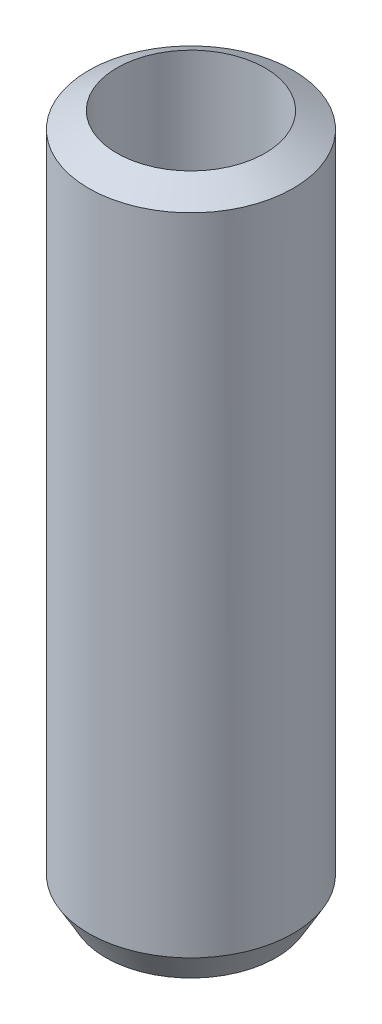
SolidWorks part; units mm, degrees
ref_plane "Front Plane" through (0, 0, 0) normal (0, 0, 1) x (1, 0, 0)
ref_plane "Top Plane" through (0, 0, 0) normal (0, 1, 0) x (1, 0, 0)
ref_plane "Right Plane" through (0, 0, 0) normal (1, 0, 0) x (0, 0, -1)
sketch "Sketch1" plane through (0, 0, 0) normal (0, 1, 0) x (1, 0, 0)
  circle A0 centre (0, 0) radius 30
  dimension "SHAFT_OD" = 60
extrude "Boss-Extrude1" add sketch "Sketch1" along normal blind 202.9932
sketch "Sketch2" plane through (0, 0, 0) normal (0, 1, 0) x (1, 0, 0)
  circle A0 centre (0, 0) radius 21.7208
  dimension "BORE_D" = 43.4416
extrude "Cut-Extrude1" cut sketch "Sketch2" along normal through all
chamfer "Chamfer1" distance 4.9891 angle 60 2 edges at (0, 202.9932, 30) (0, 0, 30) first distance on face at (0, 202.9932, 30) first distance on face at (0, 0, 21.7208)
